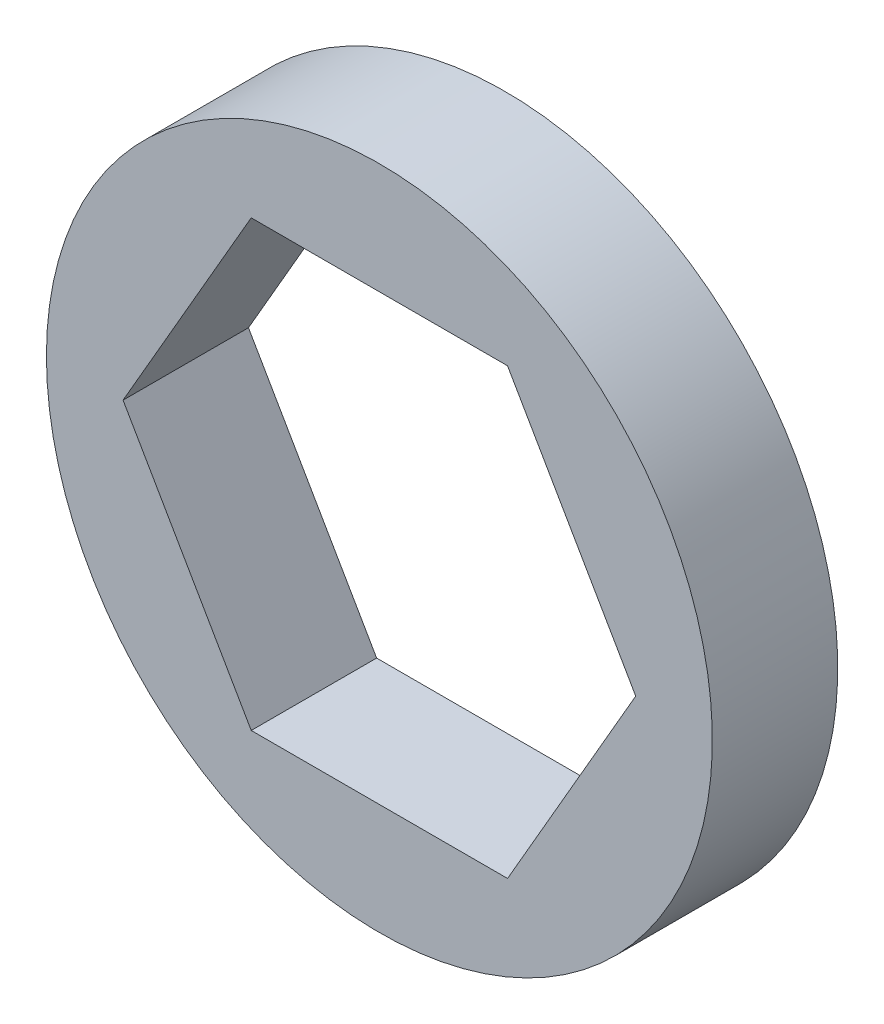
SolidWorks part; units mm, degrees
material "Nylon 101"
ref_plane "Front Plane" through (0, 0, 0) normal (0, 0, 1) x (1, 0, 0)
ref_plane "Top Plane" through (0, 0, 0) normal (0, 1, 0) x (1, 0, 0)
ref_plane "Right Plane" through (0, 0, 0) normal (1, 0, 0) x (0, 0, -1)
sketch "Sketch1" plane through (0, 0, 0) normal (0, 0, 1) x (1, 0, 0)
  line L1 (3.6662, 6.35) -> (-3.6662, 6.35)
  line L2 (-3.6662, 6.35) -> (-7.3323, 0)
  line L3 (-7.3323, 0) -> (-3.6662, -6.35)
  line L4 (-3.6662, -6.35) -> (3.6662, -6.35)
  line L5 (3.6662, -6.35) -> (7.3323, 0)
  line L6 (7.3323, 0) -> (3.6662, 6.35)
  circle A1 centre (0, 0) radius 9.525
  circle A2 centre (0, 0) radius 6.35 construction
  dimension "D1" = 19.05
  dimension ".5" = 12.7
extrude "Boss-Extrude1" add sketch "Sketch1" along normal blind 3.5875
